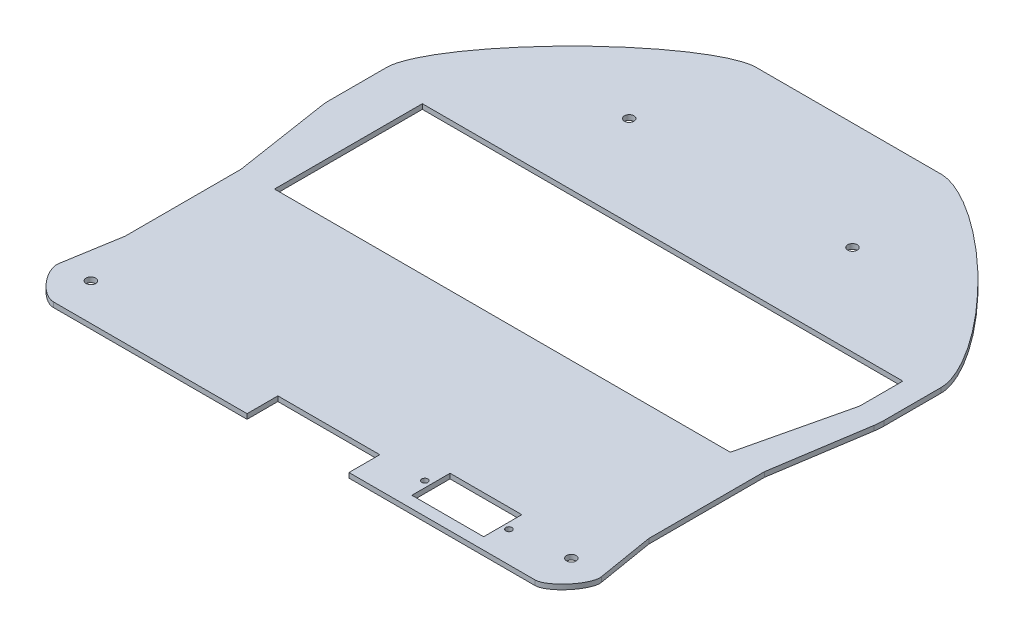
SolidWorks part; units mm, degrees
ref_plane "Front Plane" through (0, 0, 0) normal (0, 0, 1) x (1, 0, 0)
ref_plane "Top Plane" through (0, 0, 0) normal (0, 1, 0) x (1, 0, 0)
ref_plane "Right Plane" through (0, 0, 0) normal (1, 0, 0) x (0, 0, -1)
sketch "Sketch1" plane through (0, 0, 0) normal (0, 1, 0) x (1, 0, 0)
  line L0 (-90, 180) -> (-90, 0) construction
  line L1 (-180, 180) -> (0, 180)
  line L2 (-180, 180) -> (-180, 0)
  line L3 (-180, 0) -> (0, 0)
  line L4 (0, 180) -> (0, 0)
  line L5 (-180, 90) -> (0, 90) construction
  line L6 (-180, 30) -> (0, 30)
  line L7 (-130, 30) -> (-50, 30)
  line L8 (-130, 30) -> (-130, -30)
  line L9 (-130, -30) -> (-50, -30)
  line L10 (-50, 30) -> (-50, -30)
  line L11 (-130, 30) -> (-50, -30) construction
  line L12 (-130, -30) -> (-50, 30) construction
  dimension "D1" = 180
  dimension "D2" = 180
  dimension "D3" = 60
  dimension "D4" = 80
extrude "Boss-Extrude1" add sketch "Sketch1" along normal blind 1.6 contours L10 L3 L8 L9 | L2 L6 L4 L1 | L6 L10 L3 L4 | L8 L6 L2 L3 | L10 L6 L8 L3 region at (-90, 0, -105) region at (-155, 0, -15) region at (-25, 0, -15) region at (-90, 0, -15) region at (-90, 0, 15)
sketch "Sketch2" plane through (0, 1.6, 0) normal (0, 1, 0) x (1, 0, 0)
  line L0 (-180, 30) -> (0, 30)
  line L1 (-180, 180) -> (-180, 0) construction
  line L2 (0, 180) -> (0, 0) construction
  line L3 (-180, 180) -> (0, 180) construction
  line L4 (-90, 180) -> (-90, -30) construction
  line L5 (-130, -30) -> (-50, -30) construction
  dimension "D1" = 150
sketch "Sketch3" plane through (0, 1.6, 0) normal (0, 1, 0) x (1, 0, 0)
  line L0 (-180, 122) -> (0, 122)
  line L1 (-180, 180) -> (-180, 0) construction
  line L2 (0, 180) -> (0, 0) construction
  line L3 (-180, 30) -> (0, 30) construction
  dimension "D1" = 92
sketch "Sketch5" plane through (0, 1.6, 0) normal (0, 1, 0) x (1, 0, 0)
  line L0 (-114, 180) -> (-114, -30)
  line L1 (-180, 180) -> (0, 180) construction
  line L2 (-130, -30) -> (-50, -30) construction
  line L3 (-90, 180) -> (-90, -30) construction
  dimension "D1" = 24
fillet "Fillet1" radius 60 2 edges at (0, 0.8, -180) (-180, 0.8, -180) conic rho 0.2
sketch "Sketch6" plane through (0, 1.6, 0) normal (0, 1, 0) x (1, 0, 0)
  line L0 (-50, 0) -> (-130, 0)
  line L1 (-130, 0) -> (-130, -30)
  line L2 (-130, -30) -> (-50, -30)
  line L3 (-50, -30) -> (-50, 0)
  line L4 (-180, 0) -> (-175, 30.1113)
  line L5 (-175, 30.1113) -> (-175, 67.7113)
  line L6 (-175, 67.7113) -> (-180, 100)
  line L7 (-180, 120) -> (-180, 0) construction
  line L8 (-90, 180) -> (-90, -30) construction
  line L10 (-90, 180) -> (-90, 0) construction
  line L11 (0, 0) -> (-5, 30.1113)
  line L12 (-5, 30.1113) -> (-5, 67.7113)
  line L13 (-5, 67.7113) -> (0, 100)
  line M3 (0, 0) -> (0, 120)
  line M7 (-180, 120) -> (-180, 0)
  line M9 (-130, 0) -> (-130, -30)
  line M10 (-130, -30) -> (-50, -30)
  line M11 (-50, -30) -> (-50, 0)
  dimension "D1" = 37.6
  dimension "D2" = 85
  dimension "D3" = 100
extrude "Cut-Extrude1" cut sketch "Sketch6" against normal blind 10 contours L0 M11 M9 M10 | L5 L6 L4 M7 | L13 L12 L11 M3 region at (-90, 1.6, 15) region at (-177.8779, 1.6, -49.5379) region at (-2.1221, 1.6, -49.5379)
fillet "Fillet2" radius 10 2 edges at (-180, 0.8, 0) (0, 0.8, 0) conic rho 0.25
fillet "Fillet3" radius 20 2 edges at (-180, 0.8, -100) (0, 0.8, -100)
sketch "Sketch9" plane through (0, 1.6, 0) normal (0, 1, 0) x (1, 0, 0)
  line L0 (-175, 67.6) -> (-5, 67.6) construction
  line L1 (-175, 30.1113) -> (-175, 67.7113) construction
  line L2 (-5, 30.1113) -> (-5, 67.7113) construction
  line L3 (-180, 30) -> (0, 30) construction
  line L4 (-180, 115.6) -> (0, 115.6) construction
  line L5 (-180, 120) -> (-180, 101.5394) construction
  line L6 (0, 120) -> (0, 101.5394) construction
  line L7 (-16, 115.6) -> (-16, 67.6) construction
  line L8 (-90, 180) -> (-90, -30) construction
  line L9 (-164, 115.6) -> (-164, 67.6)
  line L10 (0, 101.5394) -> (-16, 101.5394) construction
  line L11 (-8, 101.5394) -> (-8, 115.6)
  line L12 (-164, 115.6) -> (-8, 115.6)
  line L14 (-16, 67.6) -> (-164, 67.6)
  line L16 (-8, 101.5394) -> (-16, 67.6)
  dimension "D1" = 37.6
  dimension "D2" = 48
  dimension "D3" = 74
  dimension "D4" = 74
extrude "Cut-Extrude3" cut sketch "Sketch9" against normal up to next
sketch "Sketch11" plane through (0, 1.6, 0) normal (0, 1, 0) x (1, 0, 0)
  line L0 (-168.2026, 0) -> (-11.7974, 0) construction
  line L1 (-175, 30.1113) -> (-175, 67.7113) construction
  line L2 (-114, 180) -> (-114, -30) construction
  line L3 (-180, 122) -> (0, 122) construction
  line L4 (-90, 180) -> (-90, 0) construction
  line L9 (-32.3, 16.2) -> (-32.3, 3.8)
  line L10 (-55.6, 3.8) -> (-55.6, 16.2)
  line L11 (-55.6, 16.2) -> (-32.3, 16.2)
  line L12 (-32.3, 3.8) -> (-55.6, 3.8)
  line L13 (-5, 30.1113) -> (-5, 67.7113) construction
  circle A0 centre (-168, 12) radius 1.55
  circle A1 centre (-126.25, 145) radius 1.55
  circle A2 centre (-12, 12) radius 1.55
  circle A3 centre (-53.75, 145) radius 1.55
  circle A4 centre (-30.3, 10) radius 1
  circle A5 centre (-57.6, 10) radius 1
  dimension "D1" = 3.1
  dimension "D2" = 12
  dimension "D4" = 3.1
  dimension "D5" = 12.25
  dimension "D6" = 23
  dimension "D7" = 2
  dimension "D8" = 2
  dimension "D3" = 7
  dimension "D9" = 23.3
  dimension "D10" = 12.4
  dimension "D11" = 3.8
  dimension "D12" = 27.3
extrude "Cut-Extrude5" cut sketch "Sketch11" against normal up to next
sketch "Sketch12" plane through (0, 1.6, 0) normal (0, 1, 0) x (1, 0, 0)
  line L1 (-168.2026, 0) -> (-11.7974, 0) construction
  line L12 (-105.3, 10) -> (-105.3, 0)
  line L13 (-105.3, 0) -> (-72.2129, 0)
  line L14 (-72.2129, 0) -> (-72.2129, 10)
  line L15 (-72.2129, 10) -> (-105.3, 10)
  circle A0 centre (-49.3, 10) radius 25 construction
  circle A1 centre (-49.3, 10) radius 56 construction
  arc A2 (-105.3, 10) -> (-104.3999, 0) centre (-49.3, 10) ccw construction
  arc A3 (-74.3, 10) -> (-72.2129, 0) centre (-49.3, 10) ccw construction
  dimension "D1" = 50
  dimension "D2" = 112
extrude "Cut-Extrude6" cut sketch "Sketch12" against normal up to next
